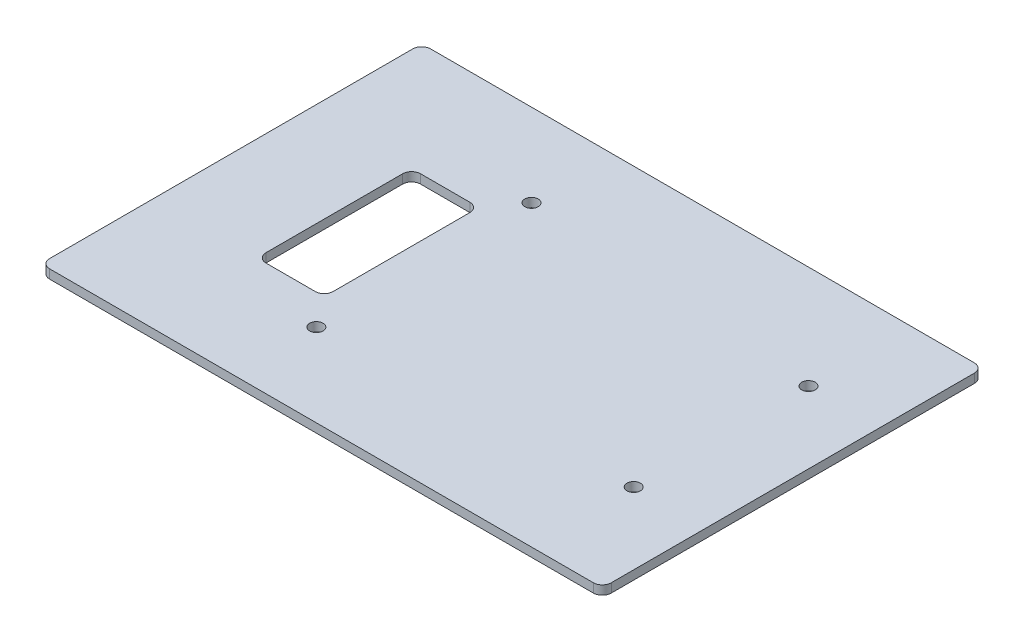
SolidWorks part; units mm, degrees
ref_plane "前视基准面" through (0, 0, 0) normal (0, 0, 1) x (1, 0, 0)
ref_plane "上视基准面" through (0, 0, 0) normal (0, 1, 0) x (1, 0, 0)
ref_plane "右视基准面" through (0, 0, 0) normal (1, 0, 0) x (0, 0, -1)
other "Configuration Table"
sketch "草图1" plane through (0, 0, 0) normal (0, 1, 0) x (1, 0, 0)
  line L0 (-39.65, 52.2066) -> (-39.65, -53.2156) construction
  line L1 (-62.65, -42.5) -> (62.65, -42.5)
  line L2 (-62.65, -42.5) -> (-62.65, 42.5)
  line L3 (-62.65, 42.5) -> (62.65, 42.5)
  line L4 (62.65, -42.5) -> (62.65, 42.5)
  line L5 (-62.65, -42.5) -> (62.65, 42.5) construction
  line L6 (-62.65, 42.5) -> (62.65, -42.5) construction
  line L7 (-1000, 0) -> (49000, 0) construction
  line L8 (46.65, 52.2199) -> (46.65, -52.2174) construction
  line L9 (-39.65, -17.25) -> (-24.65, -17.25)
  line L10 (-39.65, -17.25) -> (-39.65, 17.25)
  line L11 (-39.65, 17.25) -> (-24.65, 17.25)
  line L12 (-24.65, -17.25) -> (-24.65, 17.25)
  circle A0 centre (-19.65, 24) radius 1.5
  circle A1 centre (-19.65, -24) radius 1.5
  circle A2 centre (46.65, 19.5) radius 1.5
  circle A3 centre (46.65, -19.5) radius 1.5
  point P0 (0, 0)
  point P22 (46.65, 21.831)
  dimension "D6" = 3
  dimension "D8" = 48
  dimension "D9" = 3
  dimension "D10" = 39
  dimension "D1" = 125.3
  dimension "D2" = 85
  dimension "D3" = 23
  dimension "D4" = 15
  dimension "D5" = 34.5
  dimension "D7" = 43
  dimension "18.5" = 18.5
  dimension "16" = 16
  dimension "23" = 23
extrude "凸台-拉伸1" add sketch "草图1" along normal blind 2
fillet "圆角1" radius 2 8 edges at (-39.65, 1, 17.25) (-24.65, 1, 17.25) (-39.65, 1, -17.25) (-24.65, 1, -17.25) (-62.65, 1, -42.5) (-62.65, 1, 42.5) (62.65, 1, -42.5) (62.65, 1, 42.5)
